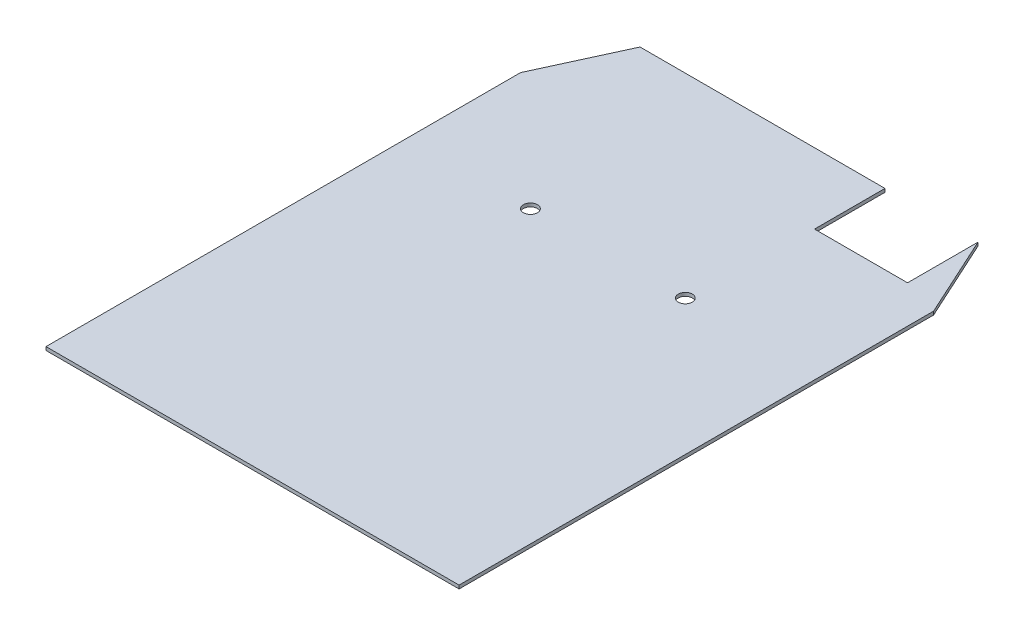
SolidWorks part; units mm, degrees
ref_plane "Front Plane" through (0, 0, 0) normal (0, 0, 1) x (1, 0, 0)
ref_plane "Top Plane" through (0, 0, 0) normal (0, 1, 0) x (1, 0, 0)
ref_plane "Right Plane" through (0, 0, 0) normal (1, 0, 0) x (0, 0, -1)
sketch "Sketch1" plane through (0, 0, 0) normal (0, 1, 0) x (1, 0, 0)
  line L0 (-96.0438, 177.8) -> (35.3219, 177.8)
  line L1 (96.0438, -177.8) -> (-96.0438, -177.8)
  line L2 (96.0438, -177.8) -> (96.0437, 177.8)
  line L4 (-96.0438, -177.8) -> (-96.0438, 177.8)
  line L5 (96.0438, -177.8) -> (-96.0438, 177.8) construction
  line L6 (96.0437, 177.8) -> (-96.0438, -177.8) construction
  line L7 (35.3219, 177.8) -> (35.3219, 145.0362)
  line L8 (35.3219, 145.0362) -> (78.5812, 145.0362)
  line L9 (78.5812, 145.0362) -> (78.5812, 177.8)
  line L10 (78.5812, 177.8) -> (96.0437, 177.8)
  point P0 (0, 0)
  dimension "D1" = 355.6
  dimension "D2" = 192.0875
  dimension "D3" = 43.2594
  dimension "D4" = 17.4625
extrude "Boss-Extrude1" add sketch "Sketch1" along normal blind 1.5875 contours L4 L0 L7 L8 L9 L10 L2 L1
sketch "Sketch2" plane through (0, 1.5875, 0) normal (0, 1, 0) x (1, 0, 0)
  line L0 (96.0438, -177.8) -> (96.0437, 177.8) construction
  line L1 (96.0438, -80.9625) -> (-96.0437, -80.9625)
  line L2 (96.0438, -80.9625) -> (96.0438, -96.8375)
  line L3 (96.0438, -96.8375) -> (-96.0438, -96.8375)
  line L4 (-96.0437, -80.9625) -> (-96.0438, -96.8375)
  line L5 (-96.0438, -177.8) -> (-96.0438, 177.8) construction
  line L6 (-78.5813, 177.8) -> (-96.0438, 139.7)
  line L7 (-96.0438, 177.8) -> (35.3219, 177.8) construction
  line L8 (-96.0438, 139.7) -> (-96.0438, 177.8)
  line L9 (-96.0438, 177.8) -> (-78.5813, 177.8)
  line L13 (96.0438, -177.8) -> (-96.0438, -177.8) construction
  line L14 (96.0437, 139.7) -> (78.5812, 177.8)
  line L15 (78.5812, 177.8) -> (96.0437, 177.8) construction
  line L16 (78.5812, 177.8) -> (96.0437, 177.8)
  line L17 (96.0437, 177.8) -> (96.0437, 139.7)
  dimension "D1" = 15.875
  dimension "D2" = 80.9625
  dimension "D3" = 38.1
extrude "Cut-Extrude1" cut sketch "Sketch2" against normal up to surface (1.5875 mm away) up to face at (28.4758, 0, -80.709)
sketch "Sketch4" plane through (0, 1.5875, 0) normal (0, 1, 0) x (1, 0, 0)
  circle A0 centre (33.0771, 87.2046) radius 3.2639
  circle A1 centre (-38.9318, 87.2046) radius 3.2639
extrude "Cut-Extrude2" cut sketch "Sketch4" against normal blind 9.906
sketch "Sketch5" plane through (0, 1.5875, 0) normal (0, 1, 0) x (1, 0, 0)
  line L1 (103.4514, -87.7438) -> (-147.3641, -87.7438)
  line L2 (103.4514, -87.7438) -> (103.4514, -226.5112)
  line L3 (103.4514, -226.5112) -> (-147.3641, -226.5112)
  line L4 (-147.3641, -87.7438) -> (-147.3641, -226.5112)
extrude "Cut-Extrude3" cut sketch "Sketch5" against normal blind 125.222
